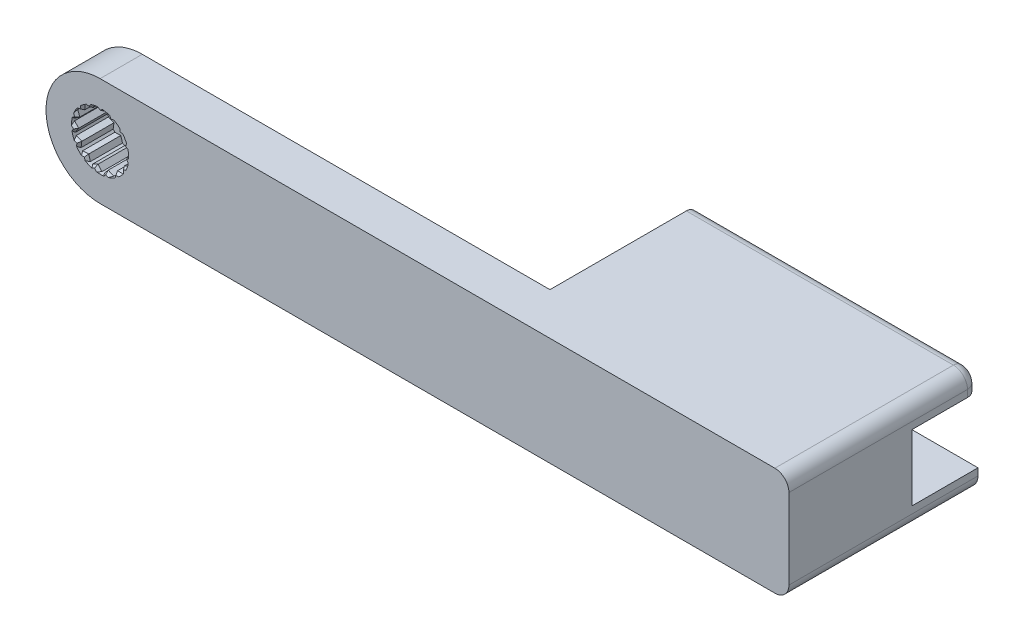
SolidWorks part; units mm, degrees
note: The reader was unsure of these and kept them because the rebuilt part matched: shared geometry of "Sketch1<4>", "Sketch1<5>", "Sketch1<6>", "Sketch1<7>".
ref_plane "Front Plane" through (0, 0, 0) normal (0, 0, 1) x (1, 0, 0)
ref_plane "Top Plane" through (0, 0, 0) normal (0, 1, 0) x (1, 0, 0)
ref_plane "Right Plane" through (0, 0, 0) normal (1, 0, 0) x (0, 0, -1)
sketch "Sketch1" plane through (0, 0, 0) normal (0, 0, 1) x (1, 0, 0)
  line L0 (0, 3.5) -> (-0.6731, 4.019)
  line L1 (0, 3.5) -> (0.6731, 4.019)
  line L2 (0, 7.7) -> (7.7, 7.7)
  line L3 (0, -7.7) -> (7.7, -7.7)
  line L4 (7.7, 7.7) -> (7.7, -7.7)
  line L5 (0, 0) -> (98, 0) construction
  line L6 (98, -4.7) -> (7.7, -4.7)
  line L7 (98, -4.7) -> (98, 4.7)
  line L8 (98, 4.7) -> (7.7, 4.7)
  line L9 (7.7, -4.7) -> (7.7, 4.7)
  line L10 (98, -4.7) -> (7.7, 4.7) construction
  line L11 (98, 4.7) -> (7.7, -4.7) construction
  line L12 (0, 0) -> (0, 9.7861) construction
  line L13 (58, 4.7) -> (98, 4.7)
  line L14 (58, 4.7) -> (58, 7.7)
  line L15 (58, 7.7) -> (98, 7.7)
  line L16 (98, 4.7) -> (98, 7.7)
  line L17 (58, 4.7) -> (58, -4.7)
  line L18 (68, -4.7) -> (98, -4.7)
  line L19 (68, -4.7) -> (68, -7.7)
  line L20 (68, -7.7) -> (98, -7.7)
  line L21 (98, -4.7) -> (98, -7.7)
  line L22 (7.7, 7.7) -> (58, 7.7)
  line L23 (7.7, -7.7) -> (68, -7.7)
  circle A0 centre (0, 0) radius 7.7
  circle A1 centre (0, 0) radius 4.075
  circle A2 centre (0, 0) radius 3.5 construction
  point P12 (52.85, 0)
  dimension "D1" = 8.15
  dimension "D2" = 7
  dimension "D3" = 15.4
  dimension "D4" = 0.85
  dimension "D5" = 9.4
  dimension "D6" = 58
  dimension "D7" = 40
  dimension "D8" = 3
  dimension "D9" = 3
  dimension "D10" = 68
  dimension "D11" = 30
extrude "outside" add sketch "Sketch1" along normal blind 5 contours A0 A1 | A0 L3 L4 L2 | A0 L3 L4 L9 | L7 L8 L4 L9 L6 | L8 L16 L15 L14 | L21 L6 L19 L20 | L17 L8 L4 L9 L6 | L22 L4 L8 L14 | L4 L23 L19 L6
extrude "single teeth" add sketch "Sketch1<4>" along normal blind 5 contours L1 A1 L0
sketch "Sketch1<4>" plane through (0, 0, 0) normal (0, 0, 1) x (1, 0, 0) same geometry as "Sketch1"
chamfer "teethChampfer" distance 0.25 angle 60 2 edges at (-0.3366, 3.7595, 5) (0.3366, 3.7595, 5)
pattern_circular "15th teeths" count 15 over 360 about axis through (0, 0, 0) along (0, 0, 1) of "single teeth", "teethChampfer"
extrude "cover" add sketch "Sketch1<5>" against normal blind 1 contours L0 A1 L1 | L1 A1 L0 | A0 A1 | A0 L3 L4 L2 | A0 L3 L4 L9 | L7 L8 L4 L9 L6 | L8 L16 L15 L14 | L21 L6 L19 L20 | L17 L8 L4 L9 L6 | L22 L4 L8 L14 | L4 L23 L19 L6
sketch "Sketch1<5>" plane through (0, 0, 0) normal (0, 0, 1) x (1, 0, 0) same geometry as "Sketch1"
extrude "gap filler" add sketch "Sketch1<6>" against normal blind 12.5 contours L8 L17 L6 L7
sketch "Sketch1<6>" plane through (0, 0, 0) normal (0, 0, 1) x (1, 0, 0) same geometry as "Sketch1"
extrude "holder" add sketch "Sketch1<7>" against normal blind 9.4 and the other way through all from vertex contours L8 L16 L15 L14 | L21 L6 L19 L20
sketch "Sketch1<7>" plane through (0, 0, 0) normal (0, 0, 1) x (1, 0, 0) same geometry as "Sketch1"
chamfer "reinfosment" distance 8 angle 20 1 edges at (68, -4.7, -6.75)
fillet "smooth" radius 2 2 edges at (98, -7.7, -8.45) (98, 7.7, -8.45)
fillet "zipTieSmoothing" radius 1.5 3 edges at (98, 5.2, -21.9) (97.4142, 7.1142, -21.9) (77, 7.7, -21.9)
equation "\"D9@Sketch1\"=\"D8@Sketch1\""
